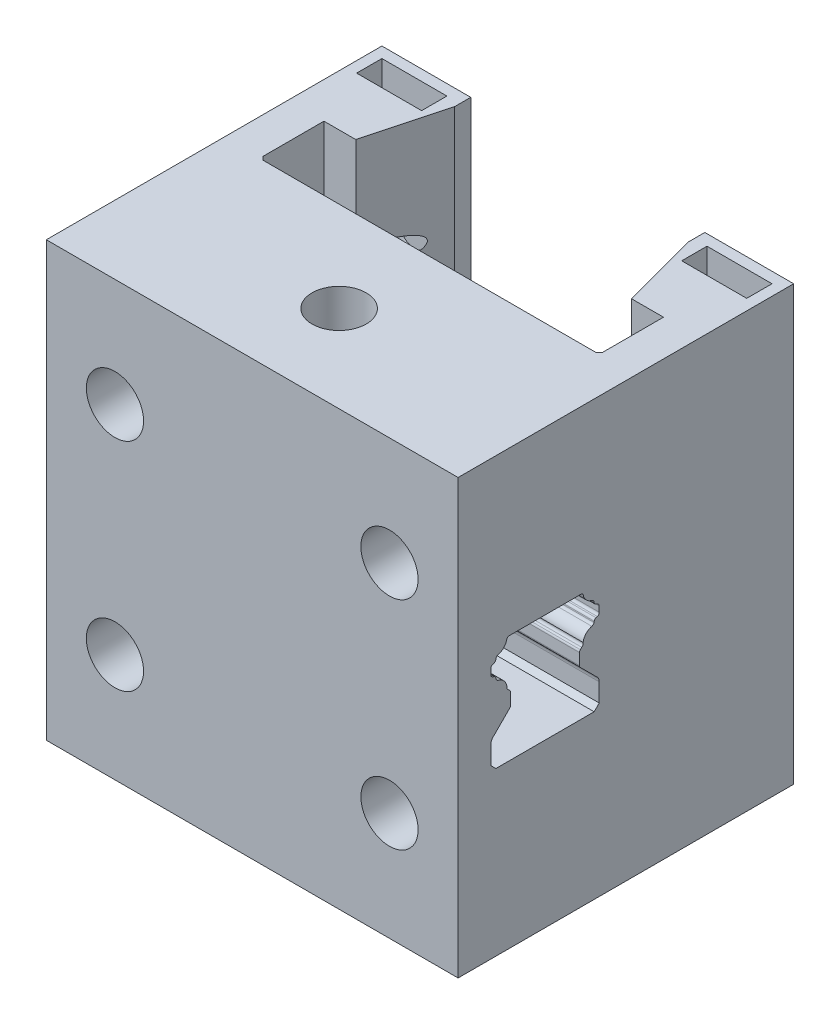
SolidWorks part; units mm, degrees
ref_plane "Front Plane" through (0, 0, 0) normal (0, 0, 1) x (1, 0, 0)
ref_plane "Top Plane" through (0, 0, 0) normal (0, 1, 0) x (1, 0, 0)
ref_plane "Right Plane" through (0, 0, 0) normal (1, 0, 0) x (0, 0, -1)
sketch "Sketch1" plane through (0, 0, 0) normal (0, 1, 0) x (1, 0, 0)
  line L0 (23.07, -9.85) -> (-23.07, -9.85)
  line L1 (-23.5, -9.42) -> (-23.07, -9.85)
  line L2 (-23.5, -9.42) -> (-23.5, -0.95)
  line L7 (-19.0939, -0.95) -> (-23.5, -0.95)
  line L8 (-19.0939, -0.95) -> (-19, -0.5997)
  line L9 (-16.2, 9.85) -> (-19, -0.5997)
  line L10 (16.2, 9.85) -> (-16.2, 9.85)
  line L11 (23.07, -9.85) -> (23.5, -9.42)
  line L12 (23.5, -2.9) -> (23.5, -9.42)
  line L13 (23.5, -2.9) -> (23.5, -0.95)
  line L15 (19.0939, -0.95) -> (23.5, -0.95)
  line L16 (19.0939, -0.95) -> (19, -0.5997)
  line L17 (16.2, 9.85) -> (19, -0.5997)
  line L18 (-28.5, -14.85) -> (28.5, -14.85)
  line L19 (-28.5, -14.85) -> (-28.5, 13.85)
  line L20 (-28.5, 13.85) -> (28.5, 13.85)
  line L21 (28.5, -14.85) -> (28.5, 13.85)
  dimension "D1" = 5
  dimension "D2" = 5
  dimension "D3" = 5
  dimension "D4" = 4
extrude "Boss-Extrude1" add sketch "Sketch1" along normal blind 60
sketch "Sketch2" plane through (0, 0, 0) normal (0, -1, 0) x (1, 0, 0)
  line L0 (0, -25.3794) -> (0, 27.4746) construction
  line L1 (28.5, -8.0706) -> (19.5, -8.0706)
  line L2 (28.5, -8.0706) -> (28.5, -12.0706)
  line L3 (28.5, -12.0706) -> (19.5, -12.0706)
  line L4 (19.5, -8.0706) -> (19.5, -12.0706)
  line L5 (-19.5, -8.0706) -> (-19.5, -12.0706)
  line L6 (-28.5, -12.0706) -> (-19.5, -12.0706)
  line L7 (-28.5, -8.0706) -> (-28.5, -12.0706)
  line L8 (-28.5, -8.0706) -> (-19.5, -8.0706)
  dimension "D1" = 9
  dimension "D2" = 4
extrude "Cut-Extrude1" cut sketch "Sketch2" against normal through all
sketch "Sketch5" plane through (0, 0, 0) normal (1, 0, 0) x (0, 0, -1)
  line L0 (-14.85, 23.2) -> (-14.85, 34.0815)
  line L1 (-15.55, 22.5) -> (-14.85, 23.2)
  line L2 (-29.15, 22.5) -> (-15.55, 22.5)
  line L3 (-29.85, 23.2) -> (-29.15, 22.5)
  line L4 (-29.85, 25.7434) -> (-29.85, 23.2)
  line L5 (-27.2372, 28.7704) -> (-29.5571, 26.4505)
  line L6 (-27.12, 30.6153) -> (-27.12, 29.0533)
  line L7 (-27.4316, 31.0926) -> (-27.2372, 30.8982)
  line L8 (-29.1562, 33.3541) -> (-29.1243, 33.2128)
  line L9 (-29.5857, 33.7052) -> (-29.4106, 33.6421)
  line L10 (-29.85, 34.8375) -> (-29.85, 34.0815)
  line L11 (-29.4277, 35.2633) -> (-29.5687, 35.2195)
  line L12 (-29.125, 35.7021) -> (-29.1553, 35.5612)
  line L13 (-27.399, 37.5) -> (-27.4361, 37.4629)
  line L14 (-17.301, 37.5) -> (-27.399, 37.5)
  line L15 (-17.2639, 37.4629) -> (-17.301, 37.5)
  line L16 (-15.5447, 35.5612) -> (-15.575, 35.7021)
  line L17 (-15.1313, 35.2195) -> (-15.2723, 35.2633)
  line L18 (-14.85, 34.0815) -> (-14.85, 60)
  line L19 (-15.2894, 33.6421) -> (-15.1143, 33.7052)
  line L20 (-15.5757, 33.2128) -> (-15.5438, 33.3541)
  line L21 (-17.4628, 30.8982) -> (-17.2684, 31.0926)
  line L22 (-17.58, 29.0533) -> (-17.58, 30.6153)
  line L23 (-15.1429, 26.4505) -> (-17.4628, 28.7704)
  line L24 (-14.85, 60) -> (-34.3805, 60)
  line L25 (-14.85, 30) -> (-29.85, 30) construction
  line L26 (-34.3805, 60) -> (-34.3805, 0)
  line L27 (-14.85, 34.0815) -> (-14.85, 30) construction
  line L28 (-34.3805, 0) -> (-14.85, 0)
  line L29 (-14.85, 0) -> (-14.85, 23.2)
  arc A0 (-14.85, 25.7434) -> (-15.1429, 26.4505) centre (-15.85, 25.7434) ccw
  arc A1 (-29.5571, 26.4505) -> (-29.85, 25.7434) centre (-28.85, 25.7434) ccw
  arc A2 (-27.2372, 28.7704) -> (-27.12, 29.0533) centre (-27.52, 29.0533) ccw
  arc A3 (-27.12, 30.6153) -> (-27.2372, 30.8982) centre (-27.52, 30.6153) ccw
  arc A4 (-27.6206, 31.5718) -> (-27.4316, 31.0926) centre (-27.2414, 31.4445) ccw
  arc A5 (-27.6206, 31.5718) -> (-28.8285, 32.9123) centre (-29.2062, 31.3576) ccw
  arc A6 (-29.1243, 33.2128) -> (-28.8285, 32.9123) centre (-28.7341, 33.301) ccw
  arc A7 (-29.1562, 33.3541) -> (-29.4106, 33.6421) centre (-29.5464, 33.2658) ccw
  arc A8 (-29.85, 34.0815) -> (-29.5857, 33.7052) centre (-29.45, 34.0815) ccw
  arc A9 (-29.5687, 35.2195) -> (-29.85, 34.8375) centre (-29.45, 34.8375) ccw
  arc A10 (-29.4277, 35.2633) -> (-29.1553, 35.5612) centre (-29.5464, 35.6453) ccw
  arc A11 (-28.8284, 36.0067) -> (-29.125, 35.7021) centre (-28.734, 35.618) ccw
  arc A12 (-28.8284, 36.0067) -> (-27.624, 37.3234) centre (-29.2062, 37.5614) ccw
  arc A13 (-27.4361, 37.4629) -> (-27.624, 37.3234) centre (-27.3021, 37.086) ccw
  arc A14 (-17.076, 37.3234) -> (-17.2639, 37.4629) centre (-17.3979, 37.086) ccw
  arc A15 (-17.076, 37.3234) -> (-15.8716, 36.0067) centre (-15.4938, 37.5614) ccw
  arc A16 (-15.575, 35.7021) -> (-15.8716, 36.0067) centre (-15.966, 35.618) ccw
  arc A17 (-15.5447, 35.5612) -> (-15.2723, 35.2633) centre (-15.1536, 35.6453) ccw
  arc A18 (-14.85, 34.8375) -> (-15.1313, 35.2195) centre (-15.25, 34.8375) ccw
  arc A19 (-15.1143, 33.7052) -> (-14.85, 34.0815) centre (-15.25, 34.0815) ccw
  arc A20 (-15.2894, 33.6421) -> (-15.5438, 33.3541) centre (-15.1536, 33.2658) ccw
  arc A21 (-15.8715, 32.9123) -> (-15.5757, 33.2128) centre (-15.9659, 33.301) ccw
  arc A22 (-15.8715, 32.9123) -> (-17.0794, 31.5718) centre (-15.4938, 31.3576) ccw
  arc A23 (-17.2684, 31.0926) -> (-17.0794, 31.5718) centre (-17.4586, 31.4445) ccw
  arc A24 (-17.4628, 30.8982) -> (-17.58, 30.6153) centre (-17.18, 30.6153) ccw
  arc A25 (-17.58, 29.0533) -> (-17.4628, 28.7704) centre (-17.18, 29.0533) ccw
  dimension "D1" = 15
  dimension "D2" = 7.5
extrude "Boss-Extrude2" add sketch "Sketch5" along normal mid plane 57 contours A18 L18 L24 L26 L28 L29 L1 L2 L3 L4 A1 L5 A2 L6 A3 L7 A4 A5 A6 L8 A7 L9 A8 L10 A9 L11 A10 L12 A11 A12 A13 L13 L14 L15 A14 A15 A16 L16 A17 L17 | L22 A25 L23 A0 L0 A19 L19 A20 L20 A21 A22 A23 L21 A24 region at (0, 11.6, 15.481) region at (0, 30.078, 15.9531)
sketch "Sketch6" plane through (0, 60, 0) normal (0, 1, 0) x (1, 0, 0)
  line L0 (0, 26.3935) -> (0, -49.3571) construction
  line L1 (28.5, 13.85) -> (-28.5, 13.85) construction
  line L2 (-7.75, 19.7454) -> (7.75, 19.7454)
  line L3 (-7.75, 19.7454) -> (-7.75, 4.3549)
  line L4 (-7.75, 4.3549) -> (7.75, 4.3549)
  line L5 (7.75, 19.7454) -> (7.75, 4.3549)
  dimension "D1" = 5.8954
  dimension "D2" = 15.5
extrude "Cut-Extrude2" cut sketch "Sketch6" against normal blind 80
sketch "Sketch9" plane through (0, 60, 0) normal (0, 1, 0) x (1, 0, 0)
  line L0 (-19.5, 13.85) -> (-19.5, 29.1706)
  line L1 (-19.5, 29.1706) -> (-28.5, 29.1706)
  line L2 (30.2, 1.2503) -> (30.2, 34.991) construction
  line L3 (-28.5, 23.1706) -> (-28.5, 8.0706) construction
  line L4 (-19.5, 12.0706) -> (-19.5, 8.0706) construction
  line L5 (-7.75, 13.85) -> (-28.5, 13.85) construction
  line L6 (-14.5, 13.85) -> (-14.5, 32.1706)
  line L7 (10, 28.7358) -> (570, 28.7358) construction
  line L10 (-14.5, 13.85) -> (-19.5, 13.85)
  line L11 (-21.75, 24.1706) -> (-28.75, 24.1706) construction
  line L12 (0, -34.3805) -> (0, 38.6423) construction
  line L13 (28.5, -34.3805) -> (-28.5, -34.3805) construction
  line L14 (-33.5, 26.1706) -> (-28.5, 26.1706)
  line L16 (-33.5, 32.1706) -> (-14.5, 32.1706)
  line L17 (-33.5, 26.1706) -> (-33.5, 32.1706)
  line L18 (-28.5, 26.1706) -> (-28.5, 29.1706)
  line L19 (28.5, 23.1706) -> (28.5, 8.0706) construction
  line L20 (30.2, 12.85) -> (30.2, 28.7358)
  line L21 (33.5, 12.85) -> (33.5, 32.1706)
  line L24 (33.5, 12.85) -> (30.2, 12.85)
  line L25 (14.5, 13.85) -> (19.5, 13.85)
  line L28 (14.5, 32.1706) -> (33.5, 32.1706)
  line L29 (14.5, 13.85) -> (14.5, 32.1706)
  line L31 (19.5, 28.7358) -> (30.2, 28.7358)
  line L32 (19.5, 13.85) -> (19.5, 28.7358)
  dimension "D1" = 5
  dimension "D2" = 3
  dimension "D3" = 3
  dimension "D4" = 5
  dimension "D5" = 5
extrude "Boss-Extrude5" add sketch "Sketch9" against normal up to surface (60 mm away) up to face at (0, 0, -2.4717)
sketch "Sketch10" plane through (0, 0, 34.3805) normal (0, 0, 1) x (1, 0, 0)
  line L0 (0, 60) -> (0, 0) construction
  line L1 (28.5, 60) -> (-28.5, 60) construction
  line L3 (-19, 45) -> (19, 45) construction
  line L4 (-19, 45) -> (-19, 15) construction
  line L5 (-19, 15) -> (19, 15) construction
  line L6 (19, 45) -> (19, 15) construction
  line L7 (-19, 45) -> (19, 15) construction
  line L8 (-19, 15) -> (19, 45) construction
  circle A0 centre (19, 45) radius 2
  circle A1 centre (19, 15) radius 2
  circle A2 centre (-19, 15) radius 2
  circle A3 centre (-19, 45) radius 2
  point P5 (0, 30)
  dimension "D3" = 4
  dimension "D1" = 30
  dimension "D2" = 38
extrude "Cut-Extrude3" cut sketch "Sketch10" against normal through all
sketch "Sketch11" plane through (0, 0, 0) normal (0, -1, 0) x (1, 0, 0)
  line L0 (28.5, -13.85) -> (19.5, -13.85) construction
  line L1 (75.7263, -13.85) -> (13.7422, -13.85)
  line L2 (75.7263, -13.85) -> (75.7263, -57.0774)
  line L3 (75.7263, -57.0774) -> (13.7422, -57.0774)
  line L4 (13.7422, -13.85) -> (13.7422, -57.0774)
  line L6 (35.2, -11.2951) -> (29.2, -11.2951)
  line L7 (35.2, -11.2951) -> (35.2, -13.8378)
  line L8 (35.2, -13.8378) -> (29.2, -13.8378)
  line L9 (29.2, -11.2951) -> (29.2, -13.8378)
  line L12 (29.2, -1.2503) -> (29.2, -34.991) construction
extrude "Cut-Extrude4" cut sketch "Sketch11" against normal through all
sketch "Sketch12" plane through (0, 0, 0) normal (0, -1, 0) x (1, 0, 0)
  line L1 (18.2699, -7.1631) -> (28.5, -7.1631)
  line L2 (18.2699, -7.1631) -> (18.2699, -13.85)
  line L3 (18.2699, -13.85) -> (28.5, -13.85)
  line L4 (28.5, -7.1631) -> (28.5, -13.85)
sketch "Sketch13" plane through (0, 0, 0) normal (0, -1, 0) x (1, 0, 0)
  line L1 (35.6591, -15.3652) -> (29.6481, -15.3652)
  line L2 (35.6591, -15.3652) -> (35.6591, -12.7446)
  line L3 (35.6591, -12.7446) -> (29.6481, -12.7446)
  line L4 (29.6481, -15.3652) -> (29.6481, -12.7446)
extrude "Cut-Extrude5" cut sketch "Sketch13" against normal through all
sketch "Sketch14" plane through (0, 0, 0) normal (0, -1, 0) x (-1, 0, 0)
  line L1 (-28.5, 12.0706) -> (-19.5, 12.0706)
  line L2 (-28.5, 12.0706) -> (-28.5, 8.0706)
  line L3 (-28.5, 8.0706) -> (-19.5, 8.0706)
  line L4 (-19.5, 12.0706) -> (-19.5, 8.0706)
extrude "Boss-Extrude7" add sketch "Sketch14" against normal through all
extrude "Boss-Extrude6" add sketch "Sketch12" against normal through all
sketch "Sketch15" plane through (0, 60, 0) normal (0, 1, 0) x (1, 0, 0)
  line L1 (-28.5, 8.0706) -> (-19.5, 8.0706)
  line L2 (-28.5, 8.0706) -> (-28.5, 12.0706)
  line L3 (-28.5, 12.0706) -> (-19.5, 12.0706)
  line L4 (-19.5, 8.0706) -> (-19.5, 12.0706)
extrude "Boss-Extrude8" add sketch "Sketch15" against normal through all
sketch "Sketch16" plane through (0, 60, 0) normal (0, 1, 0) x (1, 0, 0)
  line L0 (-28.5, 13.85) -> (-28.5, -34.3805) construction
  line L1 (-19.5, 13.85) -> (-28.5, 13.85)
  line L2 (-19.5, 13.85) -> (-19.5, 12.07)
  line L3 (-19.5, 12.07) -> (-28.5, 12.07)
  line L4 (-28.5, 13.85) -> (-28.5, 12.07)
  dimension "D1" = 1.78
extrude "Cut-Extrude6" cut sketch "Sketch16" against normal through all
sketch "Sketch17" plane through (0, 60, 0) normal (0, 1, 0) x (1, 0, 0)
  line L0 (-28.5, 12.07) -> (-19.5, 12.07) construction
  line L1 (-33.5, 12.07) -> (-7.75, 12.07)
  line L2 (-33.5, 12.07) -> (-33.5, 32.1706)
  line L3 (-33.5, 32.1706) -> (-7.75, 32.1706)
  line L4 (-7.75, 12.07) -> (-7.75, 32.1706)
  line L5 (-7.75, 13.85) -> (-7.75, 9.85) construction
extrude "Cut-Extrude7" cut sketch "Sketch17" against normal through all
sketch "Sketch18" plane through (0, 60, 0) normal (0, 1, 0) x (1, 0, 0)
  line L1 (-16.2, 9.85) -> (16.2, 9.85)
  line L2 (-16.2, 9.85) -> (-16.2, 22.4633)
  line L3 (-16.2, 22.4633) -> (16.2, 22.4633)
  line L4 (16.2, 9.85) -> (16.2, 22.4633)
extrude "Cut-Extrude8" cut sketch "Sketch18" against normal through all
sketch "Sketch19" plane through (0, 60, 0) normal (0, 1, 0) x (1, 0, 0)
  line L0 (28.5, -34.3805) -> (28.5, 13.85) construction
  line L1 (-28.5, 12.07) -> (28.5, 12.07)
  line L2 (-28.5, 12.07) -> (-28.5, 16.0198)
  line L3 (-28.5, 16.0198) -> (28.5, 16.0198)
  line L4 (28.5, 12.07) -> (28.5, 16.0198)
extrude "Cut-Extrude9" cut sketch "Sketch19" against normal through all
sketch "Sketch20" plane through (0, 60, 0) normal (0, 1, 0) x (1, 0, 0)
  line L0 (-28.5, 12.07) -> (-16.2, 12.07) construction
  line L1 (-27, 10.57) -> (-18, 10.57)
  line L2 (-27, 10.57) -> (-27, 7.07)
  line L3 (-27, 7.07) -> (-18, 7.07)
  line L4 (-18, 10.57) -> (-18, 7.07)
  line L5 (-28.5, 12.07) -> (-28.5, -34.3805) construction
  line L6 (0, -1009.85) -> (0, 48990.15) construction
  line L7 (-23.07, -9.85) -> (23.07, -9.85) construction
  line L8 (18, 10.57) -> (18, 7.07)
  line L9 (27, 7.07) -> (18, 7.07)
  line L10 (27, 10.57) -> (27, 7.07)
  line L11 (27, 10.57) -> (18, 10.57)
  point P13 (0, -9.85)
  dimension "D1" = 9
  dimension "D2" = 1.5
  dimension "D3" = 3.5
  dimension "D4" = 1.5
extrude "Cut-Extrude10" cut sketch "Sketch20" against normal through all
sketch "Sketch21" plane through (0, 0, -12.07) normal (0, 0, -1) x (-1, 0, 0)
  line L0 (28.5, 0) -> (16.2, 0) construction
  line L1 (18, 50) -> (27, 50)
  line L2 (18, 50) -> (18, 46.5)
  line L3 (18, 46.5) -> (27, 46.5)
  line L4 (27, 50) -> (27, 46.5)
  line L5 (18, 13.5) -> (27, 13.5)
  line L6 (18, 13.5) -> (18, 10)
  line L7 (18, 10) -> (27, 10)
  line L8 (27, 13.5) -> (27, 10)
  line L9 (28.5, 60) -> (16.2, 60) construction
  line L10 (28.5, 0) -> (28.5, 60) construction
  line L11 (0, 60) -> (0, 0) construction
  line L12 (23.07, 60) -> (-23.07, 60) construction
  line L13 (-27, 13.5) -> (-27, 10)
  line L14 (-18, 10) -> (-27, 10)
  line L15 (-18, 13.5) -> (-18, 10)
  line L16 (-18, 13.5) -> (-27, 13.5)
  line L17 (-27, 50) -> (-27, 46.5)
  line L18 (-18, 46.5) -> (-27, 46.5)
  line L19 (-18, 50) -> (-18, 46.5)
  line L20 (-18, 50) -> (-27, 50)
  line L21 (27, 13.5) -> (27, 10)
  dimension "D1" = 3.5
  dimension "D2" = 3.5
  dimension "D3" = 10
  dimension "D4" = 10
  dimension "D5" = 1.5
  dimension "D6" = 9
extrude "Cut-Extrude11" cut sketch "Sketch21" against normal up to surface (1.5 mm away) contours L19 L20 L17 L18 | L4 L1 L2 L3 | L8 L5 L6 L7 | L15 L16 L13 L14 region at (-22.5, 48.25, -12.07) region at (-22.5, 11.75, -12.07) region at (22.5, 11.75, -12.07) region at (22.5, 48.25, -12.07) up to face at (19.5892, 30, -10.57)
sketch "Sketch23" plane through (0, 22.5, 0) normal (0, 1, 0) x (1, 0, 0)
  line L0 (-28.5, -22.35) -> (28.5, -22.35) construction
  line L1 (-28.5, 12.07) -> (-28.5, -34.3805) construction
  line L2 (28.5, -34.3805) -> (28.5, 12.07) construction
  line L4 (-28.5, -15.55) -> (-28.5, -29.15) construction
  line L5 (-28.5, -29.15) -> (-28.5, -15.55) construction
  circle A0 centre (0, -22.35) radius 3.75
  dimension "D1" = 7.5
extrude "Cut-Extrude12" cut sketch "Sketch23" along normal through all
sketch "Sketch24" plane through (0, 22.5, 0) normal (0, 1, 0) x (1, 0, 0)
  circle A0 centre (0, -22.35) radius 2
  dimension "D1" = 4
extrude "Cut-Extrude13" cut sketch "Sketch24" against normal through all
sketch "Sketch25" plane through (0, 0, 34.3805) normal (0, 0, 1) x (1, 0, 0)
  circle A0 centre (19, 15) radius 3.961
  circle A1 centre (-19, 15) radius 3.961
  circle A2 centre (19, 45) radius 3.961
  circle A3 centre (-19, 45) radius 3.961
  dimension "D1" = 7.9219
extrude "Cut-Extrude14" cut sketch "Sketch25" against normal blind 10
